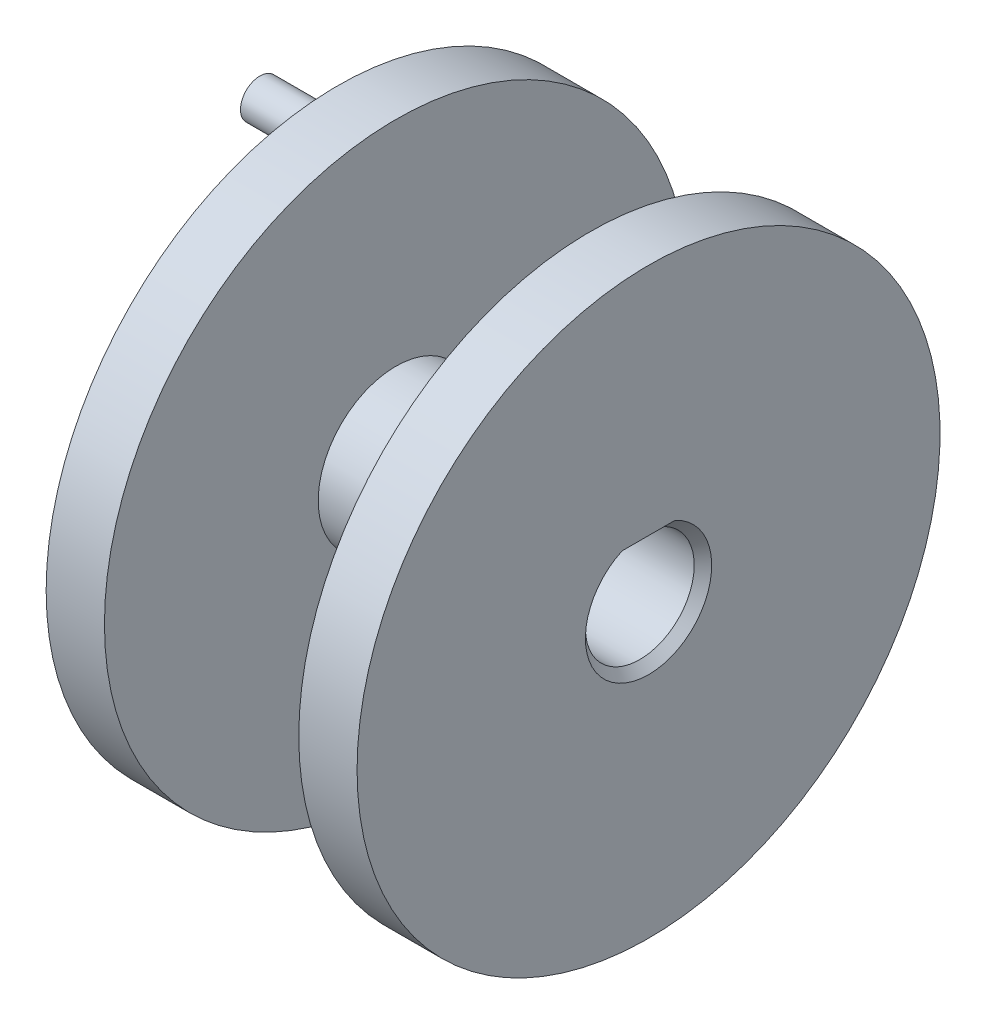
SolidWorks part; units mm, degrees
ref_plane "Front Plane" through (0, 0, 0) normal (0, 0, 1) x (1, 0, 0)
ref_plane "Top Plane" through (0, 0, 0) normal (0, 1, 0) x (1, 0, 0)
ref_plane "Right Plane" through (0, 0, 0) normal (1, 0, 0) x (0, 0, -1)
other "Center of Mass"
sketch "Sketch1" plane through (0, 0, 0) normal (1, 0, 0) x (0, 0, -1)
  line L0 (-1.3077, 2.7) -> (1.3077, 2.7) construction
  line L1 (-1.261, 2.5) -> (1.261, 2.5)
  arc A0 (-1.3077, 2.7) -> (1.3077, 2.7) centre (0, 0) ccw construction
  circle A1 centre (0, 0) radius 4
  arc A2 (-1.261, 2.5) -> (1.261, 2.5) centre (0, 0) ccw
  point P8 (0, 2.7)
  dimension "D1" = 6
  dimension "D2" = 8
  dimension "D3" = 2.6153
  dimension "D4" = 0.2
extrude "Female Shaft" add sketch "Sketch1" along normal mid plane 10
sketch "Sketch6" plane through (0, 0, 0) normal (0, 0, 1) x (1, 0, 0)
  line L2 (5, 15) -> (8, 15)
  line L3 (8, 15) -> (8, 0)
  line L4 (8, 0) -> (5, 0)
  line L5 (0, 0) -> (4.0299, 0) construction
  line L6 (5, -4) -> (5, 4) construction
  line L8 (5, 15) -> (5, 0)
  dimension "D1" = 3
  dimension "D2" = 30
revolve "Spool Edge" add sketch "Sketch6" angle 360 about L5 region at (6.5, 7.5, 0)
mirror "Spool Edge Mirror" about plane through (0, 0, 0) normal (1, 0, 0) of "Spool Edge"
extrude "Male Shaft Insert" cut sketch "Sketch1<3>" against normal through all both and the other way through all contours A0 | L1 A2 region at (0, -0.0554, 0)
sketch "Sketch1<3>" plane through (0, 0, 0) normal (1, 0, 0) x (0, 0, -1) same geometry as "Sketch1"
chamfer "Chamfer1" distance 0.45 angle 45 2 edges at (8, -2.8, 0) (8, 2.5, 0)
sketch "Sketch7" plane through (-8, 0, 0) normal (-1, 0, 0) x (0, 0, 1)
  circle A0 centre (0, 12.4335) radius 1
  dimension "D1" = 2
extrude "Boss-Extrude1" add sketch "Sketch7" along normal blind 4
